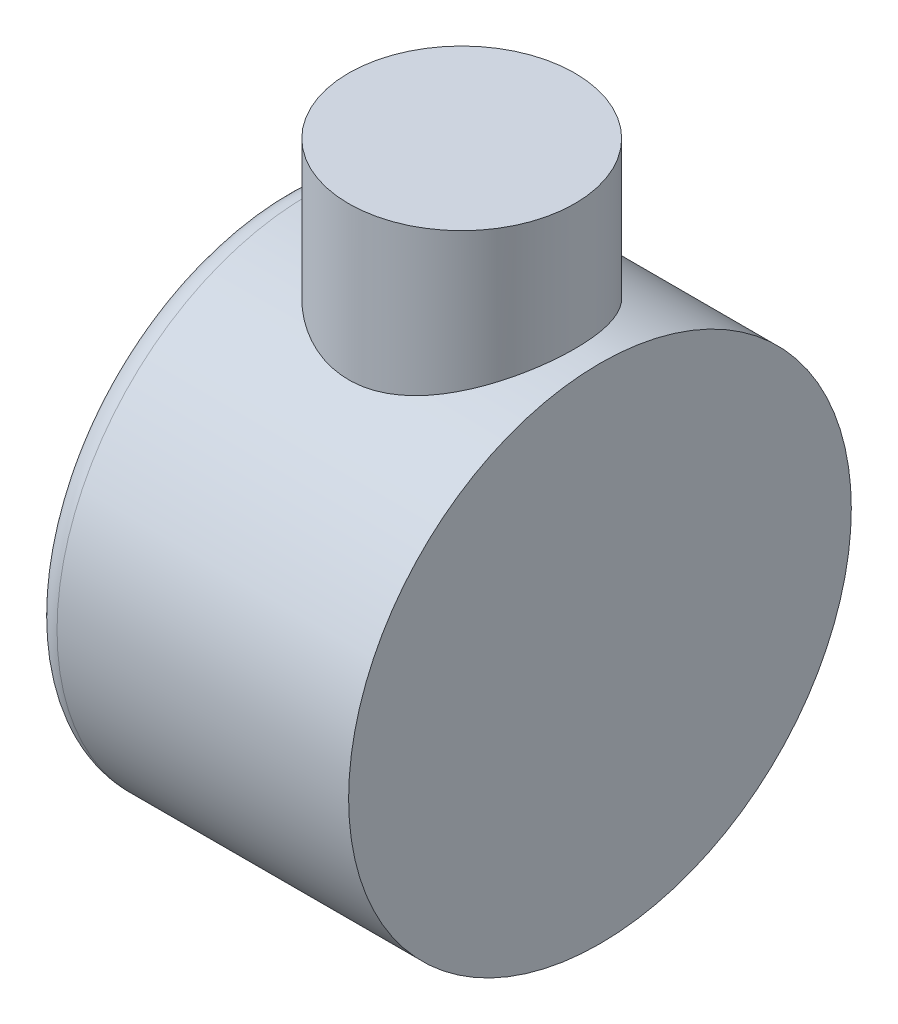
SolidWorks part; units mm, degrees
material "Cast Stainless Steel"
ref_plane "Front Plane" through (0, 0, 0) normal (0, 0, 1) x (1, 0, 0)
ref_plane "Top Plane" through (0, 0, 0) normal (0, 1, 0) x (1, 0, 0)
ref_plane "Right Plane" through (0, 0, 0) normal (1, 0, 0) x (0, 0, -1)
sketch "Sketch2" plane through (0, 0, 0) normal (1, 0, 0) x (0, 0, -1)
  circle A0 centre (0, 0) radius 50
  dimension "D1" = 100
extrude "Boss-Extrude1" add sketch "Sketch2" along normal blind 55
ref_plane "Plane1" through (27.5, 0, 0) normal (-1, 0, 0) x (0, 0, 1)
sketch "Sketch3" plane through (27.5, 0, 0) normal (-1, 0, 0) x (0, 0, 1)
  line L0 (0, 50) -> (0, 75)
  line L1 (0, 75) -> (22.5, 75)
  line L2 (0, 75) -> (-22.5, 75)
  line L3 (-22.5, 75) -> (-22.5, 44.6514)
  line L4 (22.5, 75) -> (22.5, 44.6514)
  circle A1 centre (0, 0) radius 50
  circle A2 centre (0, 0) radius 50
  dimension "D2" = 25
  dimension "D3" = 22.5
  dimension "D4" = 22.5
  dimension "D1" = 0
revolve "Revolve1" add sketch "Sketch3" angle 360 about L0 region at (27.5, 61.5818, 11.6206)
sketch "Sketch4" plane through (0, 0, 0) normal (-1, 0, 0) x (0, 0, 1)
  circle A1 centre (0, 0) radius 50
  circle A2 centre (0, 0) radius 50
  dimension "D1" = 0
extrude "Boss-Extrude2" add sketch "Sketch4" along normal blind 8
fillet "Fillet1" radius 5 1 edges at (-8, 0, 50)
ref_axis "Axis1" through (55, 0, 0) along (-1, 0, 0)
ref_axis "Axis2" through (27.5, 75, 0) along (0, -1, 0)
ref_point "Point1"
